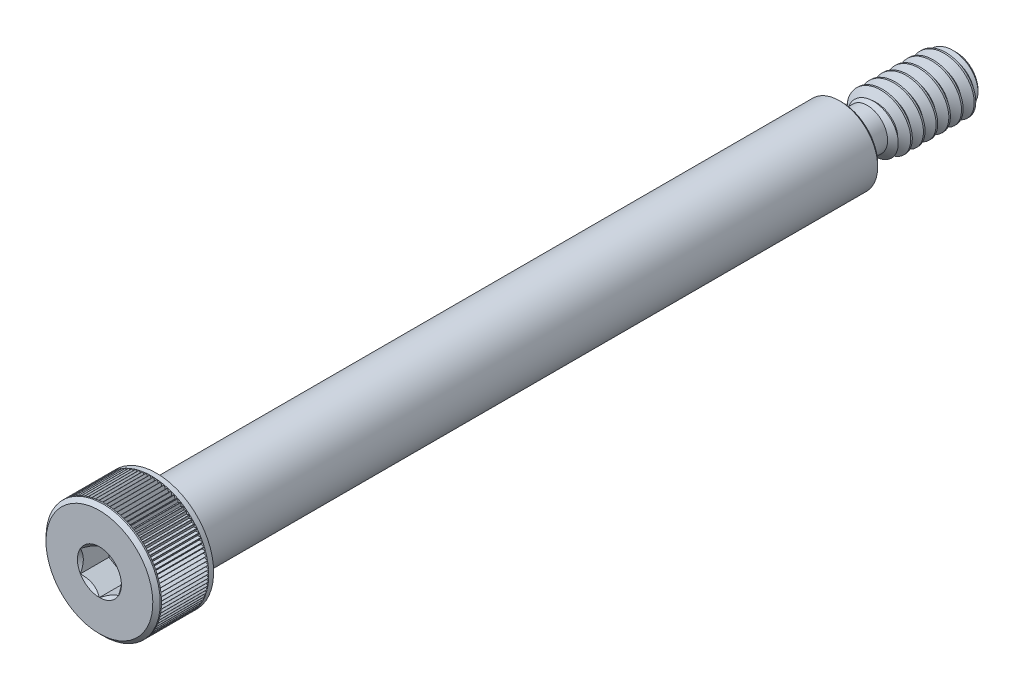
SolidWorks part; units mm, degrees
ref_plane "Front" through (0, 0, 0) normal (0, 0, 1) x (1, 0, 0)
ref_plane "Top" through (0, 0, 0) normal (0, 1, 0) x (1, 0, 0)
ref_plane "Right" through (0, 0, 0) normal (1, 0, 0) x (0, 0, -1)
sketch "Sketch1" plane through (0, 0, 0) normal (1, 0, 0) x (0, 0, -1)
  line L0 (0, 4.7625) -> (4.7625, 4.7625)
  line L1 (4.7625, 4.7625) -> (4.7625, 3.175)
  line L2 (4.7625, 3.175) -> (61.9125, 3.175)
  line L3 (61.9125, 3.175) -> (61.9125, 2.413)
  line L4 (61.9125, 2.413) -> (71.4375, 2.413)
  line L5 (71.4375, 2.413) -> (71.4375, 0)
  line L6 (71.4375, 0) -> (0, 0)
  line L7 (0, 0) -> (0, 4.7625)
  line L8 (0, 4.7625) -> (0, -4.7625) construction
  line L9 (71.4375, 2.413) -> (71.4375, -2.413) construction
  line L10 (61.9125, 3.175) -> (61.9125, -3.175) construction
  line L11 (71.4375, -2.413) -> (69.7597, -2.413) construction
  line L12 (33.3375, 0) -> (33.3375, 3.175) construction
  point P8 (69.85, -2.413)
  point P12 (61.9125, 0)
  point P17 (10.4775, 3.175)
  point P18 (33.3375, 0)
  point P19 (33.3375, 3.175)
  point P20 (56.1975, 3.175)
  point P21 (56.1975, -3.175)
  point P22 (10.4775, -3.175)
  dimension "Head Dia" = 9.525
  dimension "Head Ht" = 4.7625
  dimension "Thread Lg" = 9.525
  dimension "Thread Dia" = 4.826
  dimension "Shoulder Dia" = 6.35
  dimension "Shoulder Lg" = 57.15
  dimension "D1" = 1.5875
  dimension "D2" = 1.6778
  dimension "D3" = 28.575
  dimension "D4" = 5.715
revolve "Revolve1" add sketch "Sketch1" angle 360 mid plane about L6
ref_plane "Plane1" through (0, 0, -71.4375) normal (0, 0, 1) x (1, 0, 0)
sketch "Sketch3" plane through (0, 0, -71.4375) normal (0, 0, 1) x (1, 0, 0)
  circle A0 centre (0, 0) radius 2.413
sketch "Sketch5" plane through (0, 0, 0) normal (1, 0, 0) x (0, 0, -1)
  line L0 (61.9125, 3.175) -> (65.5066, 3.175)
  line L1 (65.5066, 3.175) -> (64.0207, 1.6891)
  line L2 (64.0207, 1.6891) -> (62.6364, 1.6891)
  line L3 (61.9125, 3.175) -> (61.9125, 2.413)
  line L5 (61.9125, 2.413) -> (71.4375, 2.413) construction
  line L6 (71.4375, 0) -> (64.0207, 0) construction
  line L7 (67.7291, 0) -> (67.7291, -2.413) construction
  arc A0 (61.9125, 2.413) -> (62.6364, 1.6891) centre (62.6364, 2.413) ccw
  dimension "D1" = 45
  dimension "CADB" = 2.1082
  dimension "CADA" = 3.3782
revolve "Cut-Revolve1" cut sketch "Sketch5" angle 360 mid plane about L6
chamfer "Chamfer1" distance 0.6032 angle 45 1 edges at (0, 2.413, -71.4375)
chamfer "Chamfer2" distance 0.3096 angle 45 1 edges at (0, 4.7625, 0)
chamfer "Chamfer3" distance 0.2032 angle 45 1 edges at (0, 3.175, -61.9125)
sketch "Sketch10" plane through (0, 0, 0) normal (1, 0, 0) x (0, 0, -1)
  line L0 (0.3096, 0) -> (4.4529, 0) construction
  line L1 (0.3096, -4.7625) -> (0.3096, 4.7625) construction
  line L3 (0.3096, 0) -> (0, 0) construction
  line L4 (4.4529, 0) -> (4.7625, 0) construction
  line L5 (4.7625, -4.7625) -> (4.7625, 4.7625) construction
  point P6 (2.3813, 0)
  dimension "D1" = 4.1434
ref_plane "Plane2" through (0, 0, -2.3813) normal (0, 0, 1) x (1, 0, 0)
sketch "Sketch11" plane through (0, 0, -2.3813) normal (0, 0, 1) x (1, 0, 0)
  line L0 (0, 4.5148) -> (0, 4.7625) construction
  line L1 (0, 4.5148) -> (0.143, 4.7625)
  line L2 (0, 4.5148) -> (-0.143, 4.7625)
  line L3 (-0.143, 4.7625) -> (0.143, 4.7625)
  line L4 (0, 0) -> (-0.143, 4.7625) construction
  line L5 (0.143, 4.7625) -> (0, 0) construction
  circle A1 centre (0, 0) radius 4.7625 construction
  circle A2 centre (0, 0) radius 4.5148 construction
  circle A3 centre (0, 0) radius 4.4529 construction
  point P3 (0, 0.0018)
  point P8 (2.3908, 0.7309)
  dimension "D1" = 0.2476
  dimension "D2" = 3.439
extrude "Cut-Extrude5" cut sketch "Sketch11" against normal mid plane 3.9362
pattern_circular "CirPattern1" count 99 over 360 about axis through (0, 0, -71.4375) along (0, 0, -1) of "Cut-Extrude5"
sketch "Sketch8" plane through (0, 0, 0) normal (0, 0, 1) x (1, 0, 0)
  line L1 (1.5875, 0.9165) -> (0, 1.8331)
  line L2 (0, 1.8331) -> (-1.5875, 0.9165)
  line L3 (-1.5875, 0.9165) -> (-1.5875, -0.9165)
  line L4 (-1.5875, -0.9165) -> (0, -1.8331)
  line L5 (0, -1.8331) -> (1.5875, -0.9165)
  line L6 (1.5875, -0.9165) -> (1.5875, 0.9165)
  circle A0 centre (0, 0) radius 1.5875 construction
  dimension "Hex" = 3.175
extrude "Cut-Extrude2" cut sketch "Sketch8" against normal blind 2.3813
sketch "Sketch9" plane through (0, 0, 0) normal (0, 0, 1) x (1, 0, 0)
  circle A0 centre (0, 0) radius 1.8331
extrude "Cut-Extrude4" cut sketch "Sketch9" against normal blind 2.3813 draft 45
sketch "Front Sketch" plane through (0, 0, 0) normal (0, 0, 1) x (1, 0, 0)
  line L0 (1.5875, -0.9165) -> (1.5875, 0.9165) construction
  line L1 (-1.5875, 0.9165) -> (-1.5875, -0.9165) construction
  circle A0 centre (0, 0) radius 4.7625 construction
  point P4 (-1.5875, 0)
  point P5 (1.5875, 0)
  point P6 (4.7625, 0)
  point P9 (-4.7625, 0)
ref_plane "Contact Plane 1" through (0, 0, -4.7625) normal (0, 0, -1) x (-1, 0, 0)
ref_axis "Center Axis 1" through (0, 0, -71.4375) along (0, 0, 1)
curve "Helix/Spiral1" pitch 1.0583 height 10.5833 radius 2.413 centre (0, 0, -71.4375) axis (0, 0, 1) start towards (0, 1, 0)
sketch "Sketch4" plane through (0, 0, 0) normal (1, 0, 0) x (0, 0, -1)
  line L0 (71.3714, 2.5276) -> (72.4297, 2.5276) construction
  line L1 (72.4297, 2.5276) -> (71.9005, 1.611) construction
  line L3 (71.9005, 1.611) -> (71.3714, 2.5276) construction
  line L4 (71.4044, 2.4703) -> (72.3966, 2.4703) construction
  line L5 (71.4375, 2.413) -> (72.3635, 2.413) construction
  line L6 (71.8344, 1.7256) -> (71.9667, 1.7256) construction
  line L7 (71.9005, 1.7256) -> (71.9005, 1.611) construction
  line L8 (71.9005, 2.5276) -> (71.9005, 2.413) construction
  line L9 (71.4044, 2.4703) -> (72.3966, 2.4703)
  line L10 (72.3966, 2.4703) -> (71.9667, 1.7256)
  line L11 (71.9667, 1.7256) -> (71.8344, 1.7256)
  line L12 (71.8344, 1.7256) -> (71.4044, 2.4703)
  point P14 (71.9005, 2.4703)
  point P15 (71.9005, 2.5276)
  dimension "D1" = 1.0583
  dimension "D2" = 0.1323
sweep "Cut-Sweep1" cut profiles "Sketch4" path "Helix/Spiral1" align with end faces yes
sketch "Sketch12" plane through (0, 0, 0) normal (1, 0, 0) x (0, 0, -1)
  line L1 (61.9125, 2.9718) -> (61.7093, 3.175)
  line L2 (61.7093, 3.175) -> (4.7625, 3.175)
  line L3 (4.7625, 3.175) -> (4.7625, 0)
  line L4 (4.7625, -4.7625) -> (4.7625, 4.7625) construction
  line L5 (4.7625, 0) -> (61.9125, 0)
  line L6 (61.9125, 2.9718) -> (61.9125, 2.413)
  line L7 (64.0207, 1.6891) -> (62.6364, 1.6891) construction
  line L8 (64.0207, 1.6891) -> (62.6364, 1.6891)
  line L9 (64.0207, 1.6891) -> (64.0207, 0)
  line L10 (64.0207, 0) -> (61.9125, 0)
  arc A0 (61.9125, 2.413) -> (62.6364, 1.6891) centre (62.6364, 2.413) ccw construction
  arc A1 (61.9125, 2.413) -> (62.6364, 1.6891) centre (62.6364, 2.413) ccw
revolve "Revolve2" add sketch "Sketch12" angle 360 about L5
equation "\"D3@Helix/Spiral1\" = \"Thread Lg@Sketch1\" + \"D4@Helix/Spiral1\""
equation "\"D1@Chamfer1\" = \"Thread Dia@Sketch1\" * .125"
equation "\"D1@Cut-Extrude2\"= \"Head Ht@Sketch1\" * .5"
equation "\"D1@Cut-Extrude4\" = \"D1@Cut-Extrude2\""
equation "\"D1@Chamfer2\" = \"Head Dia@Sketch1\" * .0325"
equation "\"D1@Sketch1\"=\"D4@Helix/Spiral1\"*1.5"
equation "\"D1@Sketch11\"=\"D1@Chamfer2\"*.8"
equation "\"D1@Cut-Extrude5\"=\"D1@Sketch10\"*.95"
equation "\"D1@CirPattern1\"=(360/\"D2@Sketch11\")-6"
equation "\"D3@Sketch1\"=\"Shoulder Lg@Sketch1\"/2"
equation "\"D4@Sketch1\"=\"D3@Sketch1\"*.2"
equation "\"D1@Sketch4\"=\"D4@Helix/Spiral1\""
equation "\"D2@Sketch4\"=\"D1@Sketch4\"/8"
